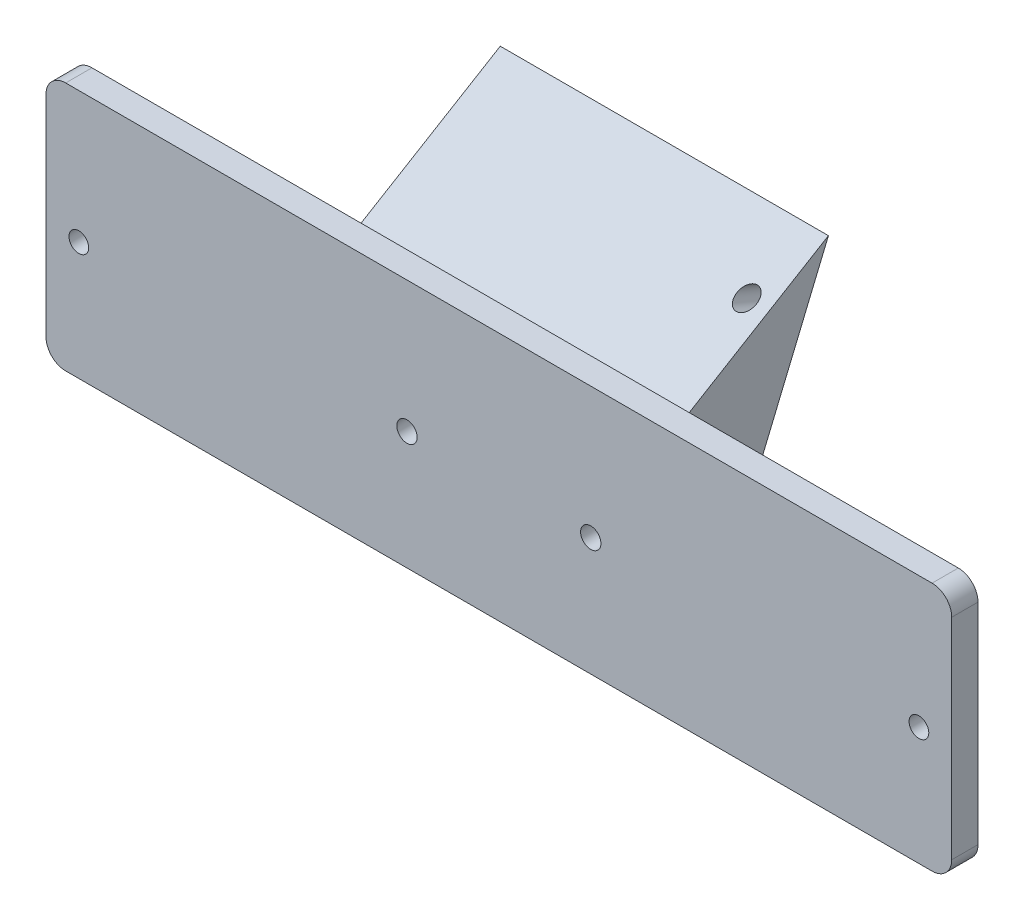
SolidWorks part; units mm, degrees
ref_plane "Alzado" through (0, 0, 0) normal (0, 0, 1) x (1, 0, 0)
ref_plane "Planta" through (0, 0, 0) normal (0, 1, 0) x (1, 0, 0)
ref_plane "Vista lateral" through (0, 0, 0) normal (1, 0, 0) x (0, 0, -1)
sketch "Croquis1" plane through (0, 0, 0) normal (0, 0, 1) x (1, 0, 0)
  line L1 (-66, -19) -> (66, -19)
  line L2 (-69, -16) -> (-69, 16)
  line L3 (-66, 19) -> (66, 19)
  line L4 (69, -16) -> (69, 16)
  line L5 (-69, -19) -> (69, 19) construction
  line L6 (-69, 19) -> (69, -19) construction
  arc A0 (66, -19) -> (69, -16) centre (66, -16) ccw
  arc A1 (66, 19) -> (69, 16) centre (66, 16) cw
  arc A2 (-66, -19) -> (-69, -16) centre (-66, -16) cw
  arc A3 (-69, 16) -> (-66, 19) centre (-66, 16) cw
  point P0 (0, 0)
  dimension "D3" = 3
  dimension "D4" = 3
  dimension "D5" = 3
  dimension "D6" = 3
  dimension "D1" = 138
  dimension "D2" = 38
extrude "Saliente-Extruir1" add sketch "Croquis1" along normal blind 4
sketch "Croquis2" plane through (0, 0, 0) normal (0, 0, 1) x (1, 0, 0)
  line L0 (0, -28.1683) -> (0, 34.9437) construction
  line L1 (0, 0) -> (92.6876, 0) construction
  line L2 (92.6876, 0) -> (-76.7898, 0) construction
  line L6 (66, 19) -> (-66, 19) construction
  line L7 (-69, 16) -> (-69, -16) construction
  circle A1 centre (-64, -1) radius 1.5
  circle A2 centre (64, -1) radius 1.5
  dimension "D1" = 20
  dimension "D2" = 3
  dimension "D3" = 5
extrude "Cortar-Extruir1" cut sketch "Croquis2" against normal blind 4 and the other way blind 13
sketch "Croquis4" plane through (69, 0, 0) normal (1, 0, 0) x (0, 0, -1)
  line L0 (0, -19) -> (21.2115, 31.7452)
  line L1 (21.2115, 31.7452) -> (0, 19)
  line L3 (0, 16) -> (0, 19) construction
  line L5 (0, 19) -> (0, -19)
  point P9 (0, 19)
  dimension "D1" = 59
  dimension "D2" = 55
extrude "Saliente-Extruir5" add sketch "Croquis4" against normal blind 94
sketch "Croquis6" plane through (69, 0, 0) normal (1, 0, 0) x (0, 0, -1)
  line L0 (0, -19) -> (0, 19)
  line L1 (0, 19) -> (21.2115, 31.7452)
  line L2 (21.2115, 31.7452) -> (0, -19)
extrude "Cortar-Extruir2" cut sketch "Croquis6" against normal blind 44
sketch "Croquis10" plane through (0, 0, 4) normal (0, 0, 1) x (1, 0, 0)
  line L0 (0, 0) -> (0, 19) construction
  line L2 (66, 19) -> (-66, 19) construction
  circle A0 centre (-14, -1) radius 1.55
  circle A2 centre (14, -1) radius 1.55
  point P8 (0, 0)
  dimension "D1" = 3.1
  dimension "D2" = 20
  dimension "D3" = 14
extrude "Cortar-Extruir3" cut sketch "Croquis10" against normal blind 44 and the other way blind 44
sketch "Croquis15" plane through (0, 0, 0) normal (0, 0, 1) x (1, 0, 0)
  line L1 (0, 36.6157) -> (0, 0) construction
  circle A0 centre (14, -1) radius 4
  circle A1 centre (-14, -1) radius 4
  dimension "D1" = 8
extrude "Cortar-Extruir5" cut sketch "Croquis15" against normal blind 14
sketch "Croquis17" plane through (0, -2.826, -6.7607) normal (0, -0.3857, -0.9226) x (-1, 0, 0)
  line L0 (25, 37.4699) -> (-25, 37.4699) construction
  line L1 (-25, -17.5301) -> (-25, 37.4699) construction
  circle A0 centre (-21.6, 28.9699) radius 1.5
  dimension "D1" = 3
  dimension "D2" = 8.5
  dimension "D3" = 3.4
extrude "Cortar-Extruir6" cut sketch "Croquis17" against normal blind 16
sketch "Croquis19" plane through (0, -2.826, -6.7607) normal (0, -0.3857, -0.9226) x (-1, 0, 0)
  line L0 (25, -17.5301) -> (25, 37.4699) construction
  line L1 (25, -17.5301) -> (-25, -17.5301) construction
  line L2 (22, -4.5301) -> (-12, -4.5301) construction
  circle A0 centre (22, -4.5301) radius 1.55
  circle A1 centre (-12, -4.5301) radius 1.55
  dimension "D1" = 3.1
  dimension "D5" = 3.1
  dimension "D2" = 3
  dimension "D3" = 13
  dimension "D4" = 34
extrude "Cortar-Extruir9" cut sketch "Croquis19" against normal blind 9 and the other way blind 18
